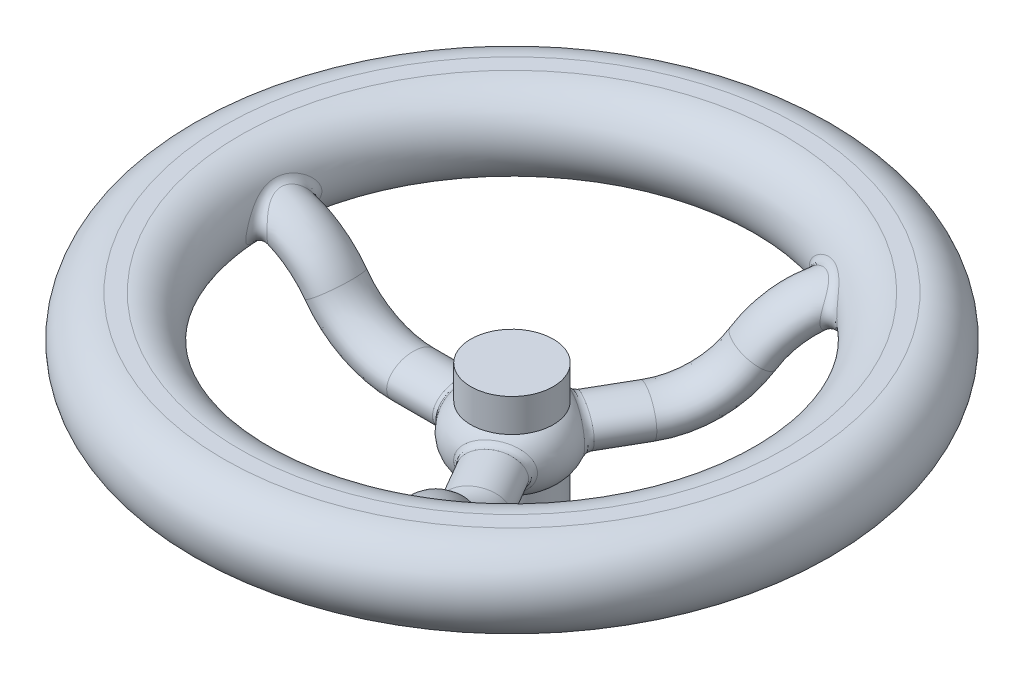
SolidWorks part; units mm, degrees
material "Сталь"
ref_plane "Спереди" through (0, 0, 0) normal (0, 0, 1) x (1, 0, 0)
ref_plane "Сверху" through (0, 0, 0) normal (0, 1, 0) x (1, 0, 0)
ref_plane "Справа" through (0, 0, 0) normal (1, 0, 0) x (0, 0, -1)
sketch "Эскиз1" plane through (0, 0, 0) normal (0, 0, 1) x (1, 0, 0)
  line L0 (-12.5, 35) -> (-12.5, 45)
  line L1 (0, 0) -> (-12.5, 0)
  line L2 (0, 0) -> (0, 45) construction
  line L3 (0, 45) -> (-12.5, 45)
  line L4 (-12.5, 0) -> (-12.5, 19)
  line L5 (0, 0) -> (0, 45)
  arc A0 (-12.5, 35) -> (-12.5, 19) centre (-6.5, 27) ccw
  dimension "D4" = 4
  dimension "D1" = 25
  dimension "D2" = 45
  dimension "D3" = 16
  dimension "D5" = 10
revolve "Повернуть1" add sketch "Эскиз1" angle 360 about L2
sketch "Эскиз2" plane through (0, 0, 0) normal (0, 0, 1) x (1, 0, 0)
  line L0 (-87.5, 51) -> (-82.5, 51) construction
  line L1 (-87.5, 63.5) -> (-82.5, 63.5)
  line L2 (-87.5, 38.5) -> (-82.5, 38.5)
  line L3 (0, 0) -> (0, 105.4539) construction
  line L4 (12.5, 45) -> (-12.5, 45) construction
  arc A0 (-87.5, 63.5) -> (-87.5, 38.5) centre (-87.5, 51) ccw
  arc A1 (-82.5, 38.5) -> (-82.5, 63.5) centre (-82.5, 51) ccw
  point P2 (-85, 51)
  dimension "D4" = 30
  dimension "D1" = 170
  dimension "D2" = 6
  dimension "D3" = 25
revolve "Повернуть2" add sketch "Эскиз2" angle 360 about L3
sketch "Эскиз3" plane through (0, 0, 0) normal (0, 0, 1) x (1, 0, 0)
  line L0 (0, 27) -> (-30, 27)
  line L1 (0, 0) -> (0, 105.4539) construction
  line L2 (-76.9894, 51) -> (-85, 51)
  line L3 (-87.5, 51) -> (-82.5, 51) construction
  line L4 (-16.5, 27) -> (16.5, 27) construction
  arc A0 (-30, 27) -> (-53.4947, 39) centre (-30, 56) cw
  arc A1 (-53.4947, 39) -> (-76.9894, 51) centre (-76.9894, 22) ccw
  arc A2 (-12.5, 35) -> (-12.5, 19) centre (-6.5, 27) ccw construction
  arc A3 (12.5, 19) -> (12.5, 35) centre (6.5, 27) ccw construction
  dimension "D1" = 29
  dimension "D2" = 55
sketch "Эскиз4" plane through (0, 0, 0) normal (1, 0, 0) x (0, 0, -1)
  ellipse E0 centre (0, 27) end of major axis (8, 27) minor radius 6
  dimension "D1" = 12
  dimension "D2" = 16
sweep "По траектории1" add profiles "Эскиз4" path "Эскиз3"
fillet "Скругление1" radius 3 2 edges at (-14.4353, 25.9951, 7.887) (-69.5685, 50.1839, 7.9977)
pattern_circular "Круговой массив1" count 3 over 360 about axis through (0, 0, 0) along (0, -1, 0) of "По траектории1", "Скругление1"
